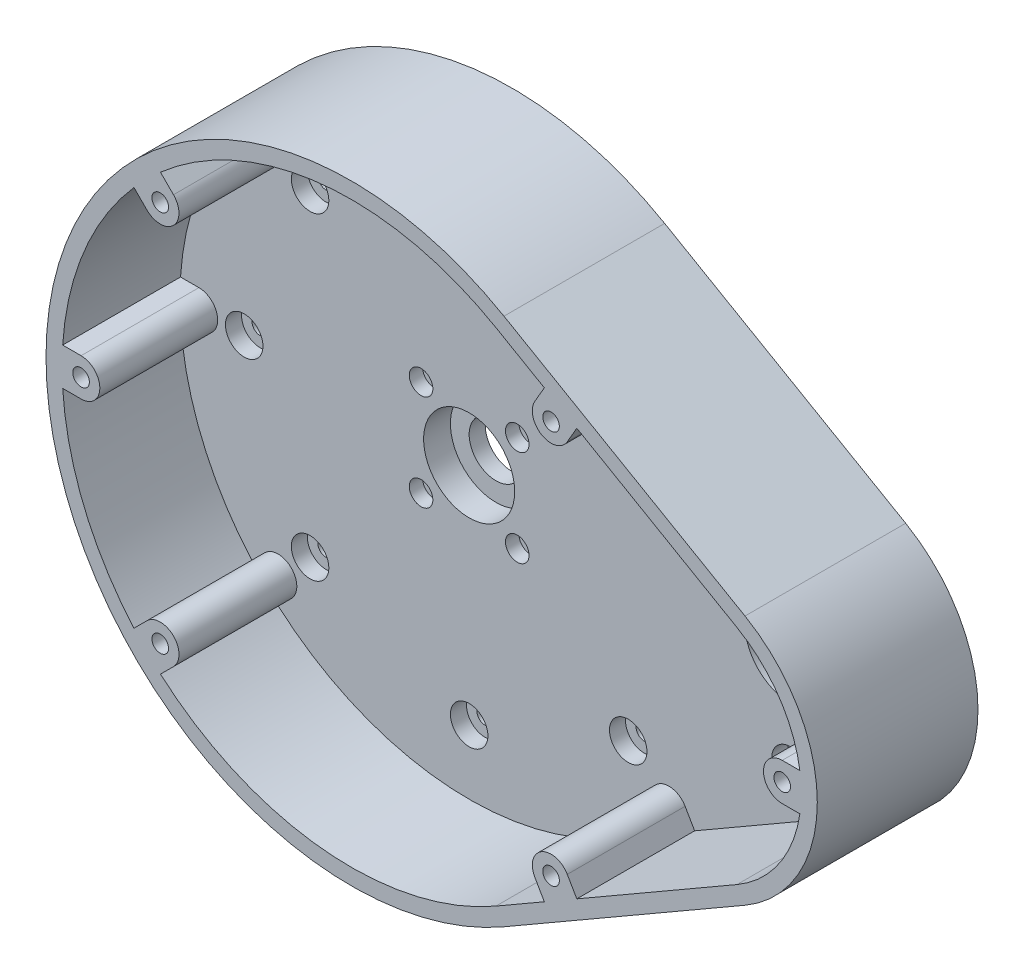
SolidWorks part; units mm, degrees
ref_plane "Front Plane" through (0, 0, 0) normal (0, 0, 1) x (1, 0, 0)
ref_plane "Top Plane" through (0, 0, 0) normal (0, 1, 0) x (1, 0, 0)
ref_plane "Right Plane" through (0, 0, 0) normal (1, 0, 0) x (0, 0, -1)
sketch "Sketch1" plane through (0, 0, 0) normal (0, 0, 1) x (1, 0, 0)
  line L0 (-30, 0) -> (30, 0) construction
  line L3 (-1.5, 49.3634) -> (43.5, 23.3827)
  line L4 (-1.5, -49.3634) -> (43.5, -23.3827)
  circle A0 centre (-30, 0) radius 57 construction
  circle A1 centre (30, 0) radius 27 construction
  circle A4 centre (-30, 0) radius 46.5 construction
  circle A5 centre (30, 0) radius 16.5 construction
  arc A6 (-1.5, 49.3634) -> (-1.5, -49.3634) centre (-30, 0) ccw
  arc A7 (43.5, 23.3827) -> (43.5, -23.3827) centre (30, 0) cw
  point P4 (0, 0)
extrude "Boss-Extrude1" add sketch "Sketch1" along normal blind 30 contours L4 A7 L3 A6
sketch "Sketch3" plane through (0, 0, 30) normal (0, 0, 1) x (1, 0, 0)
  line L3 (6.7696, 36.7696) -> (-66.7696, -36.7696) construction
  line L4 (-66.7696, -36.7696) -> (-65.6735, -35.6735) construction
  line L7 (-82, 0) -> (-80.45, 0) construction
  line L8 (50.45, 3.5259) -> (53.7396, 3.5259)
  line L9 (50.45, -3.4741) -> (53.7472, -3.4741)
  line L10 (-4, 45.0333) -> (41, 19.0526) construction
  line L11 (-4, -45.0333) -> (41, -19.0526) construction
  line L29 (-80.45, 3.5) -> (-83.8865, 3.5)
  line L30 (-80.45, -3.5) -> (-83.8865, -3.5)
  line L34 (-68.1484, -33.1987) -> (-63.1987, -38.1484) construction
  line L36 (27.2243, -57.2243) -> (-87.2243, 57.2243) construction
  line L37 (-66.7696, 36.7696) -> (-65.6735, 35.6735) construction
  line L38 (-68.1484, 33.1987) -> (-63.1987, 38.1484) construction
  line L39 (-63.1987, 38.1484) -> (-65.6286, 40.5784)
  line L40 (-68.1484, 33.1987) -> (-70.5784, 35.6286)
  line L41 (-68.1484, -33.1987) -> (-70.5784, -35.6286)
  line L45 (8.0666, 38.0666) -> (7.2916, 36.7243) construction
  line L46 (10.3227, 34.9743) -> (4.2606, 38.4743) construction
  line L49 (8.0666, -38.0666) -> (7.2916, -36.7243) construction
  line L50 (4.2606, -38.4743) -> (10.3227, -34.9743) construction
  line L51 (10.3227, -34.9743) -> (12.0977, -38.0487)
  line L52 (4.2606, -38.4743) -> (6.0356, -41.5487)
  line L53 (42, -20.7846) -> (12.0977, -38.0487)
  line L56 (-3, -46.7654) -> (6.0356, -41.5487)
  line L57 (-65.6286, -40.5784) -> (-63.1987, -38.1484)
  line L58 (42, 20.7846) -> (-3, 46.7654) construction
  line L59 (10.3227, 34.9743) -> (12.0977, 38.0487)
  line L60 (4.2606, 38.4743) -> (6.0356, 41.5487)
  line L61 (-3, 46.7654) -> (6.0356, 41.5487)
  line L62 (12.0977, 38.0487) -> (42, 20.7846)
  circle A6 centre (-30, 0) radius 52 construction
  circle A7 centre (30, 0) radius 22 construction
  arc A12 (50.45, -3.4741) -> (50.45, 3.5259) centre (50.45, 0.0259) cw
  circle A13 centre (50.45, 0.0259) radius 1.55
  arc A22 (42, 20.7846) -> (53.7396, 3.5259) centre (30, 0) cw
  arc A23 (53.7472, -3.4741) -> (42, -20.7846) centre (30, 0) cw
  arc A30 (-65.6286, 40.5784) -> (-3, 46.7654) centre (-30, 0) cw
  arc A32 (-70.5784, 35.6286) -> (-83.8865, 3.5) centre (-30, 0) ccw
  circle A41 centre (-80.45, 0) radius 1.55
  arc A42 (-80.45, 3.5) -> (-80.45, -3.5) centre (-80.45, 0) cw
  circle A44 centre (-65.6735, 35.6735) radius 1.55
  arc A45 (-63.1987, 38.1484) -> (-68.1484, 33.1987) centre (-65.6735, 35.6735) cw
  circle A51 centre (7.2916, -36.7243) radius 1.55
  arc A52 (4.2606, -38.4743) -> (10.3227, -34.9743) centre (7.2916, -36.7243) cw
  arc A53 (-83.8865, -3.5) -> (-70.5784, -35.6286) centre (-30, 0) ccw
  arc A54 (-65.6286, -40.5784) -> (-3, -46.7654) centre (-30, 0) ccw
  circle A55 centre (-65.6735, -35.6735) radius 1.55
  arc A56 (-68.1484, -33.1987) -> (-63.1987, -38.1484) centre (-65.6735, -35.6735) cw
  circle A57 centre (-30, 0) radius 54 construction
  circle A58 centre (7.2916, 36.7243) radius 1.55
  arc A59 (4.2606, 38.4743) -> (10.3227, 34.9743) centre (7.2916, 36.7243) ccw
  point P10 (-30, 0)
  point P20 (-30, 0)
  point P22 (-30, 0)
  point P32 (-30, 0)
  point P35 (-30, 0)
  point P37 (-30, 0)
  point P39 (-30, 0)
  point P45 (-65.6735, 35.6735)
  point P51 (-30, 0)
  point P56 (-65.6735, -35.6735)
  point P59 (-30, 0)
  point P68 (7.2916, 36.7243)
  point P85 (7.2916, -36.7243)
extrude "Cut-Extrude1" cut sketch "Sketch3" against normal blind 22
sketch "Sketch5" plane through (0, 0, 0) normal (0, 0, -1) x (-1, 0, 0)
  circle A12 centre (65.6735, 35.6735) radius 1.55
  circle A13 centre (80.45, 0) radius 1.55
  circle A15 centre (-50.45, 0.0259) radius 1.55
  circle A16 centre (-7.2916, -36.7243) radius 1.55
  circle A18 centre (65.6735, -35.6735) radius 1.55
  circle A19 centre (-7.2916, 36.7243) radius 1.55
extrude "Cut-Extrude2" cut sketch "Sketch5" against normal blind 30
sketch "Sketch6" plane through (0, 0, 0) normal (0, 0, -1) x (-1, 0, 0)
  circle A12 centre (-50.45, 0.0259) radius 3.5
  circle A13 centre (-7.2916, -36.7243) radius 3.5
  circle A15 centre (80.45, 0) radius 3.5
  circle A16 centre (65.6735, 35.6735) radius 3.5
  circle A18 centre (65.6735, -35.6735) radius 3.5
  circle A19 centre (-7.2916, 36.7243) radius 3.5
extrude "Cut-Extrude3" cut sketch "Sketch6" against normal blind 5
sketch "Sketch7" plane through (0, 0, 8) normal (0, 0, 1) x (1, 0, 0)
  line L0 (-30, 0) -> (30, 0) construction
  circle A4 centre (-30, 0) radius 8.5
  circle A6 centre (30, 0) radius 8.5
extrude "Cut-Extrude10" cut sketch "Sketch7" against normal blind 5
sketch "Sketch8" plane through (0, 0, 8) normal (0, 0, 1) x (1, 0, 0)
  line L0 (-30, 0) -> (-38.9803, 8.9803) construction
  circle A0 centre (-30, 0) radius 5
  circle A1 centre (-30, 0) radius 12.7 construction
  circle A2 centre (-38.9803, 8.9803) radius 1.05
  circle A3 centre (-21.0197, 8.9803) radius 1.05
  circle A4 centre (-21.0197, -8.9803) radius 1.05
  circle A5 centre (-38.9803, -8.9803) radius 1.05
  point P7 (-30, 0)
  point P10 (-30, 0)
  point P17 (-30, 0)
  dimension "D1" = 4
extrude "Cut-Extrude7" cut sketch "Sketch8" against normal blind 8
sketch "Sketch9" plane through (0, 0, 8) normal (0, 0, 1) x (1, 0, 0)
  circle A0 centre (-38.9803, 8.9803) radius 2.2
  circle A1 centre (-21.0197, 8.9803) radius 2.2
  circle A2 centre (-21.0197, -8.9803) radius 2.2
  circle A3 centre (-38.9803, -8.9803) radius 2.2
  point P12 (-30, 0)
  dimension "D1" = 4
extrude "Cut-Extrude8" cut sketch "Sketch9" against normal blind 2.5
sketch "Sketch10" plane through (0, 0, 30) normal (0, 0, 1) x (1, 0, 0)
  line L0 (-3.0003, 46.7655) -> (42, 20.7849)
  line L2 (-3.0003, -46.7655) -> (42, -20.7849)
  line L3 (-4, 45.0333) -> (41, 19.0526)
  line L4 (-4, -45.0333) -> (41, -19.0526)
  circle A0 centre (-30, 0) radius 54 construction
  circle A1 centre (30, 0) radius 24.0003 construction
  arc A2 (-3.0003, 46.7655) -> (-3.0003, -46.7655) centre (-30, 0) ccw
  arc A3 (42, 20.7849) -> (42, -20.7849) centre (30, 0) cw
  circle A4 centre (-30, 0) radius 52 construction
  circle A5 centre (30, 0) radius 22 construction
  arc A6 (41, 19.0526) -> (41, -19.0526) centre (30, 0) cw
  arc A7 (-4, 45.0333) -> (-4, -45.0333) centre (-30, 0) ccw
sketch "Sketch11" plane through (0, 0, 8) normal (0, 0, 1) x (1, 0, 0)
  line L0 (-30, 0) -> (-0.3015, 29.6985) construction
  line L1 (30, -19) -> (30, 19) construction
  line L2 (30, 0) -> (42, 0) construction
  circle A0 centre (-30, 0) radius 42 construction
  circle A1 centre (-0.3015, 29.6985) radius 1.55
  circle A2 centre (-30, 42) radius 1.55
  circle A3 centre (-59.6985, 29.6985) radius 1.55
  circle A4 centre (-72, 0) radius 1.55
  circle A5 centre (-59.6985, -29.6985) radius 1.55
  circle A6 centre (-30, -42) radius 1.55
  circle A7 centre (-0.3015, -29.6985) radius 1.55
  circle A8 centre (30, 19) radius 1.55
  circle A9 centre (30, -19) radius 1.55
  point P19 (-30, 0)
  point P24 (30, 0)
  dimension "D1" = 7
extrude "Cut-Extrude11" cut sketch "Sketch11" against normal blind 8
sketch "Sketch12" plane through (0, 0, 8) normal (0, 0, 1) x (1, 0, 0)
  line L0 (-0.3015, 29.6985) -> (-30, 0) construction
  circle A0 centre (-0.3015, 29.6985) radius 3.5
  circle A1 centre (-30, 42) radius 3.5
  circle A2 centre (-59.6985, 29.6985) radius 3.5
  circle A3 centre (-72, 0) radius 3.5
  circle A4 centre (-59.6985, -29.6985) radius 3.5
  circle A5 centre (-30, -42) radius 3.5
  circle A6 centre (-0.3015, -29.6985) radius 3.5
  circle A7 centre (30, 19) radius 3.5
  circle A9 centre (30, -19) radius 3.5
  point P20 (-30, 0)
  dimension "D1" = 7
extrude "Cut-Extrude12" cut sketch "Sketch12" against normal blind 3
